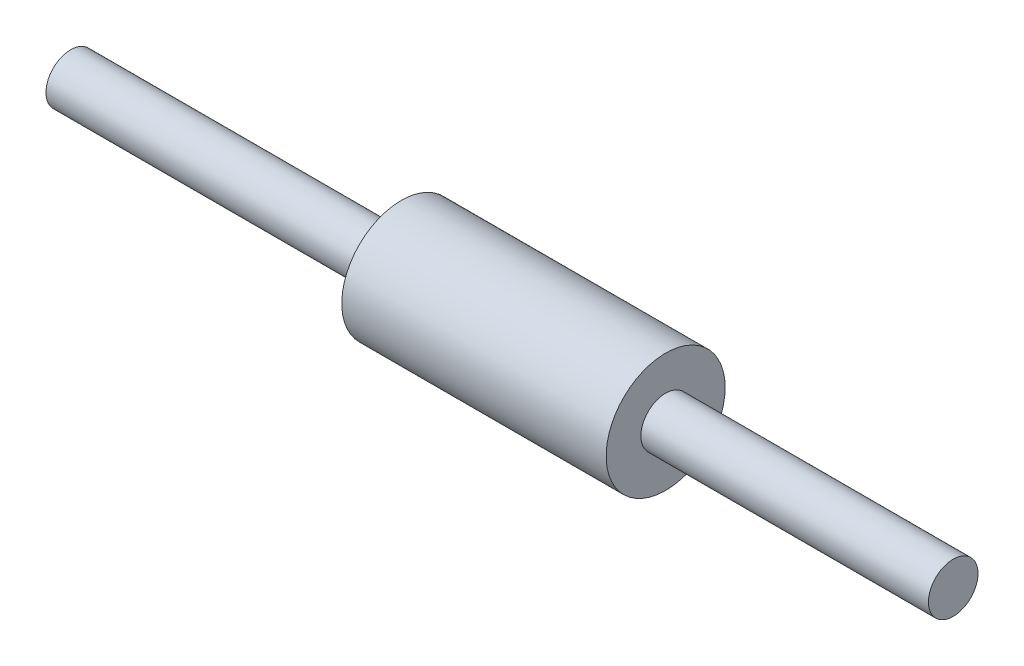
SolidWorks part; units mm, degrees
ref_plane "Front Plane" through (0, 0, 0) normal (0, 0, 1) x (1, 0, 0)
ref_plane "Top Plane" through (0, 0, 0) normal (0, 1, 0) x (1, 0, 0)
ref_plane "Right Plane" through (0, 0, 0) normal (1, 0, 0) x (0, 0, -1)
sketch "Sketch1" plane through (0, 0, 0) normal (0, 0, 1) x (1, 0, 0)
  line L0 (196.3562, 0) -> (-196.3562, 0) construction
  line L3 (127, 7.5) -> (-140, 7.5)
  line L4 (0, -42.6677) -> (0, 42.6677) construction
  line L7 (127, 7.5) -> (127, 0)
  line L8 (127, 0) -> (-127, 0)
  line L9 (-140, 7.5) -> (-140, 6.5)
  line L10 (-140, 6.5) -> (-127, 6.5)
  line L11 (-127, 6.5) -> (-127, 0)
  line L12 (-40, 18) -> (40, 18)
  line L13 (-40, 18) -> (-40, 7.5)
  line L14 (40, 18) -> (40, 7.5)
  point P3 (0, 18)
  point P10 (0, 0)
  dimension "D1" = 127
  dimension "D2" = 140
  dimension "D3" = 13
  dimension "D4" = 15
  dimension "D5" = 13
  dimension "D6" = 36
  dimension "D7" = 80
revolve "Revolve1" add sketch "Sketch1" angle 360 about L0 region at (-0.9048, 3.772, 0) region at (0, 12.75, 0) other way angle 360
